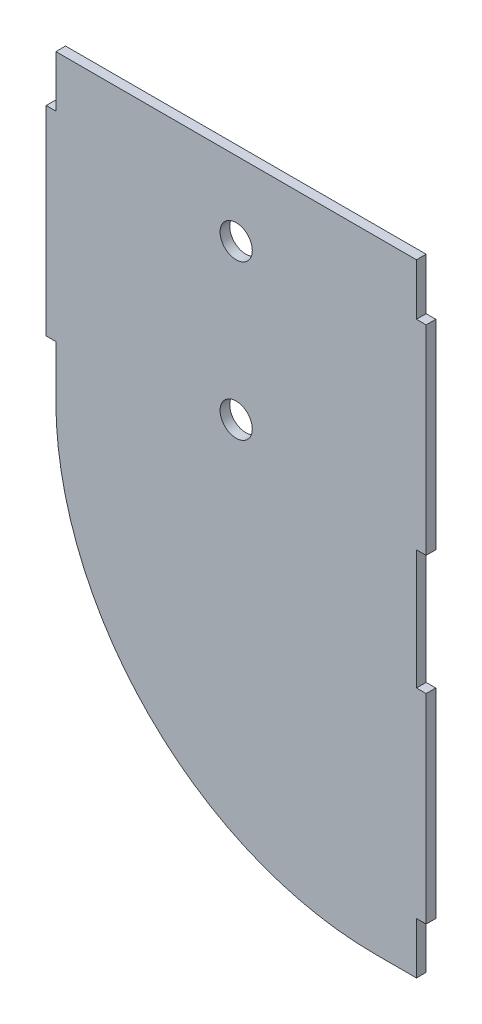
SolidWorks part; units mm, degrees
ref_plane "Front Plane" through (0, 0, 0) normal (0, 0, 1) x (1, 0, 0)
ref_plane "Top Plane" through (0, 0, 0) normal (0, 1, 0) x (1, 0, 0)
ref_plane "Right Plane" through (0, 0, 0) normal (1, 0, 0) x (0, 0, -1)
sketch "Sketch1" plane through (0, 0, 0) normal (0, 0, 1) x (1, 0, 0)
  line L0 (0, 74.6125) -> (-177.8, 74.6125)
  line L1 (0, 87.3125) -> (4.7625, 87.3125) construction
  line L2 (-177.8, 65.0875) -> (-177.8, -65.0875) construction
  line L4 (-177.8, 74.6125) -> (-177.8, 49.2125)
  line L5 (-177.8, 49.2125) -> (-182.5625, 49.2125)
  line L6 (-20.3679, -232.0446) -> (0, -232.0446)
  line L7 (0, -238.3946) -> (0, -206.6446) construction
  line L8 (0, -232.0446) -> (0, -206.6446)
  line L9 (-177.8, -74.6125) -> (-177.8, -49.2125)
  line L10 (-177.8, -49.2125) -> (-182.5625, -49.2125)
  line L11 (0, -206.6446) -> (4.7625, -206.6446) construction
  line L12 (-182.5625, -49.2125) -> (-182.5625, 49.2125)
  line L14 (0, -206.6446) -> (4.7625, -206.6446)
  line L15 (0, 65.0875) -> (0, 80.9625) construction
  line L16 (0, 74.6125) -> (0, 49.2125)
  line L17 (0, -65.0875) -> (0, 65.0875) construction
  line L18 (4.7625, -206.6446) -> (4.7625, -108.2196)
  line L20 (4.7625, -108.2196) -> (0, -108.2196)
  line L22 (0, -108.2196) -> (0, -49.2125) construction
  line L23 (0, -108.2196) -> (0, -49.2125)
  line L24 (0, -49.2125) -> (4.7625, -49.2125)
  line L25 (4.7625, -49.2125) -> (4.7625, 49.2125)
  line L26 (4.7625, 49.2125) -> (0, 49.2125)
  line L27 (4.7625, -244.7446) -> (0, -244.7446) construction
  arc A4 (-20.3679, -232.0446) -> (-177.8, -74.6125) centre (-20.3679, -74.6125) cw
  dimension "D1" = 12.7
  dimension "D2" = 12.7
extrude "Extrude1" add sketch "Sketch1" against normal blind 4.7625
sketch "Sketch2" plane through (0, 0, 0) normal (0, 0, 1) x (1, 0, 0)
  line L0 (-88.9, 38.1) -> (-88.9, -38.1) construction
  line L1 (0, 74.6125) -> (-177.8, 74.6125) construction
  line L3 (0, 0) -> (-88.9, 0) construction
  circle A0 centre (-88.9, 38.1) radius 7.9375
  circle A1 centre (-88.9, -38.1) radius 7.9375
  point P5 (-88.9, 74.6125)
  dimension "D2" = 76.2
  dimension "D1" = 15.875
extrude "Cut-Extrude1" cut sketch "Sketch2" against normal up to next
